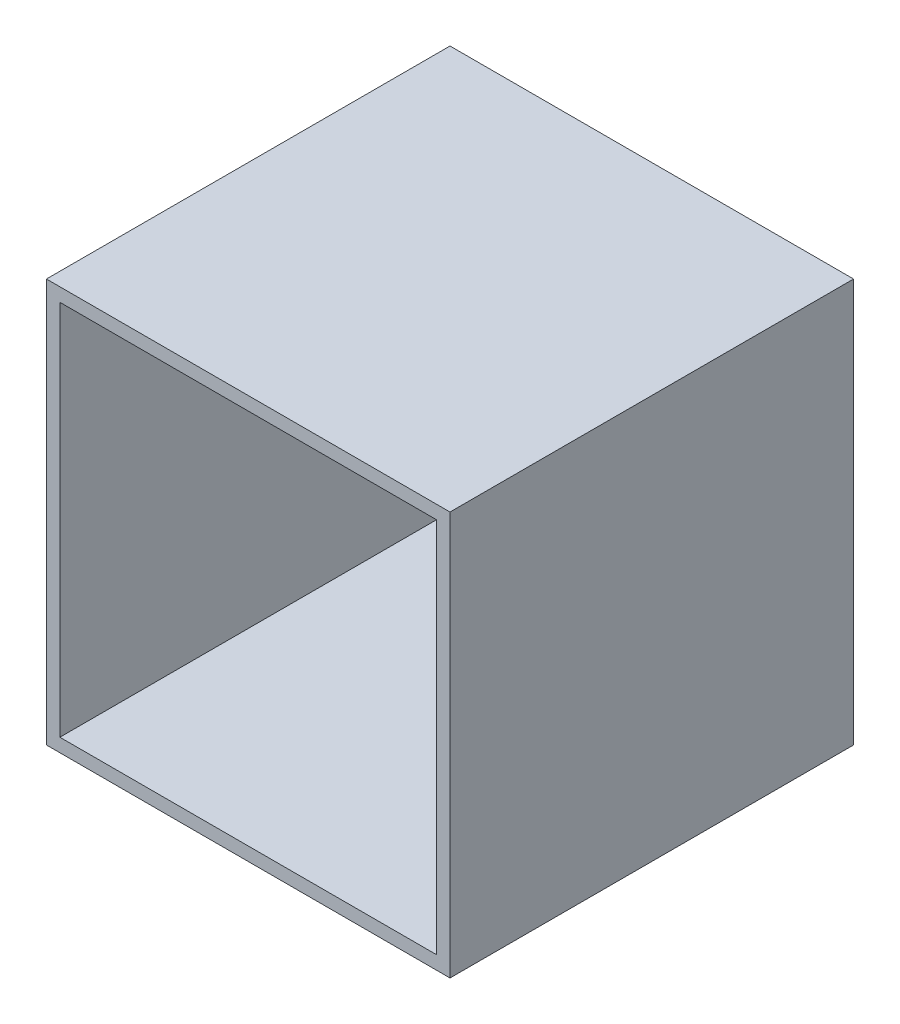
SolidWorks part; units mm, degrees
ref_plane "Front Plane" through (0, 0, 0) normal (0, 0, 1) x (1, 0, 0)
ref_plane "Top Plane" through (0, 0, 0) normal (0, 1, 0) x (1, 0, 0)
ref_plane "Right Plane" through (0, 0, 0) normal (1, 0, 0) x (0, 0, -1)
sketch "Sketch1" plane through (0, 0, 0) normal (0, 1, 0) x (1, 0, 0)
  line L1 (-38.1, -38.1) -> (38.1, -38.1)
  line L2 (-38.1, -38.1) -> (-38.1, 38.1)
  line L3 (-38.1, 38.1) -> (38.1, 38.1)
  line L4 (38.1, -38.1) -> (38.1, 38.1)
  line L5 (-38.1, -38.1) -> (38.1, 38.1) construction
  line L6 (-38.1, 38.1) -> (38.1, -38.1) construction
  point P0 (0, 0)
  dimension "D1" = 76.2
  dimension "D2" = 76.2
extrude "box" add sketch "Sketch1" along normal blind 76.2
shell "hollow it" thickness 2.54 removed face at (0, 38.1, 38.1)
sketch "Sketch2" plane through (0, 0, -38.1) normal (0, 0, -1) x (-1, 0, 0)
  line L0 (-38.1, 76.2) -> (38.1, 76.2) construction
  line L1 (-27.94, 69.85) -> (-20.32, 69.85)
  line L2 (-27.94, 69.85) -> (-27.94, 6.35)
  line L3 (-27.94, 6.35) -> (-20.32, 6.35)
  line L4 (-20.32, 69.85) -> (-20.32, 6.35)
  line L6 (-38.1, 76.2) -> (-38.1, 0) construction
  dimension "D1" = 7.62
  dimension "D2" = 63.5
  dimension "D3" = 6.35
  dimension "D4" = 10.16
extrude "slider track" cut sketch "Sketch2" against normal up to surface (2.54 mm away) up to face at (0, 38.1, -35.56)
sketch "Sketch4" plane through (0, 0, -38.1) normal (0, 0, -1) x (-1, 0, 0)
  line L0 (-38.1, 76.2) -> (38.1, 76.2) construction
  circle A0 centre (0, 63.5) radius 6.35
  dimension "D1" = 12.7
  dimension "D2" = 12.7
extrude "button large ring" cut sketch "Sketch4" against normal blind 1.27
sketch "Sketch5" plane through (0, 0, -36.83) normal (0, 0, -1) x (-1, 0, 0)
  circle A0 centre (0, 63.5) radius 3.556
  circle A1 centre (0, 63.5) radius 6.35 construction
  dimension "D2" = 7.112
  dimension "D1" = 0
extrude "button small hole" cut sketch "Sketch5" against normal blind 1.27
sketch "Sketch6" plane through (0, 0, -38.1) normal (0, 0, -1) x (-1, 0, 0)
  line L0 (-3.2977, 25.4) -> (-3.2977, 31.75)
  line L1 (-3.2977, 31.75) -> (3.0523, 31.75)
  line L2 (3.0523, 31.75) -> (3.0523, 25.4)
  line L3 (3.0523, 25.4) -> (9.4023, 25.4)
  line L4 (9.4023, 25.4) -> (9.4023, 19.05)
  line L5 (9.4023, 19.05) -> (3.0523, 19.05)
  line L6 (3.0523, 19.05) -> (3.0523, 12.7)
  line L7 (3.0523, 12.7) -> (-3.2977, 12.7)
  line L8 (-3.2977, 12.7) -> (-3.2977, 19.05)
  line L9 (-3.2977, 19.05) -> (-9.6477, 19.05)
  line L10 (-9.6477, 19.05) -> (-9.6477, 25.4)
  line L11 (-9.6477, 25.4) -> (-3.2977, 25.4)
  line L12 (-38.1, 0) -> (38.1, 0) construction
  dimension "D1" = 6.35
  dimension "D2" = 6.35
  dimension "D3" = 6.35
  dimension "D4" = 6.35
  dimension "D5" = 6.35
  dimension "D6" = 6.35
  dimension "D7" = 6.35
  dimension "D8" = 6.35
  dimension "D9" = 6.35
  dimension "D10" = 12.7
extrude "dpad large shape" cut sketch "Sketch6" against normal blind 1.27
sketch "Sketch7" plane through (0, 0, -36.83) normal (0, 0, -1) x (-1, 0, 0)
  line L0 (-3.2977, 25.4) -> (-9.6477, 25.4) construction
  line L1 (-9.6477, 25.4) -> (-9.6477, 19.05) construction
  line L2 (3.0523, 12.7) -> (3.0523, 19.05) construction
  line L3 (-3.2977, 12.7) -> (3.0523, 12.7) construction
  line L4 (3.0523, 19.05) -> (9.4023, 19.05) construction
  line L5 (9.4023, 19.05) -> (9.4023, 25.4) construction
  line L6 (3.0523, 25.4) -> (3.0523, 31.75) construction
  line L7 (-3.2977, 31.75) -> (-3.2977, 25.4) construction
  line L8 (3.0523, 31.75) -> (-3.2977, 31.75) construction
  circle A0 centre (-0.1227, 28.575) radius 1.397
  circle A1 centre (6.2273, 22.225) radius 1.397
  circle A2 centre (-0.1227, 15.875) radius 1.397
  circle A3 centre (-6.4727, 22.225) radius 1.397
  point P12 (3.0523, 15.875)
  point P17 (6.2273, 19.05)
  dimension "D3" = 2.794
  dimension "D6" = 2.794
  dimension "D9" = 2.794
  dimension "D13" = 2.794
  dimension "D1" = 3.175
  dimension "D2" = 3.175
  dimension "D4" = 3.175
  dimension "D5" = 3.175
  dimension "D7" = 3.175
  dimension "D8" = 3.175
  dimension "D10" = 3.175
  dimension "D11" = 3.175
  dimension "D12" = 3.175
extrude "dpad tiny holes" cut sketch "Sketch7" against normal blind 1.27
sketch "Sketch8" plane through (0, 0, -38.1) normal (0, 0, -1) x (-1, 0, 0)
  line L0 (38.1, 76.2) -> (38.1, 0) construction
  circle A0 centre (21.336, 43.0507) radius 12.7
  dimension "D1" = 25.4
  dimension "D2" = 16.764
extrude "dial large ring" cut sketch "Sketch8" against normal blind 1.27
ref_point "dial center"
sketch "Sketch9" plane through (0, 0, -36.83) normal (0, 0, -1) x (-1, 0, 0)
  circle A0 centre (21.336, 43.0507) radius 5.08
  dimension "D1" = 10.16
extrude "dial small hole" cut sketch "Sketch9" against normal blind 1.27
sketch "Sketch10" plane through (0, 73.66, 0) normal (0, -1, 0) x (1, 0, 0)
  line L0 (35.56, -35.56) -> (-35.56, -35.56) construction
  line L1 (-35.56, -35.56) -> (-35.56, 38.1) construction
  circle A0 centre (-12.7, -13.563) radius 3.81
  point P2 (0, -35.56)
  dimension "D1" = 25.4
  dimension "D2" = 22.86
extrude "obstruction for baton" add sketch "Sketch10" along normal blind 20.32
